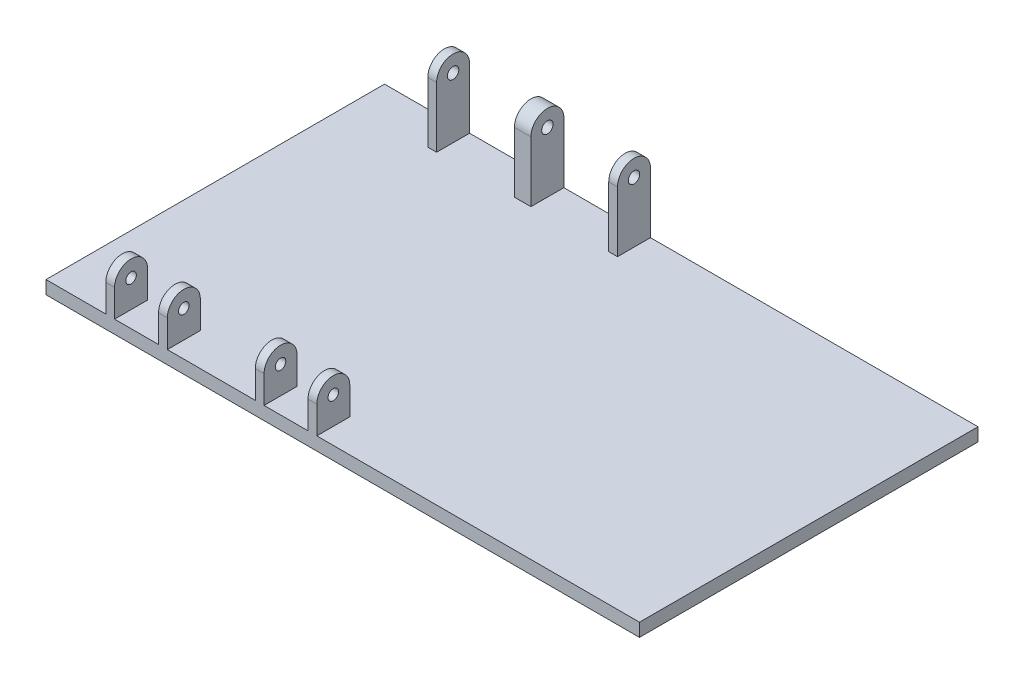
SolidWorks part; units mm, degrees
ref_plane "Front Plane" through (0, 0, 0) normal (0, 0, 1) x (1, 0, 0)
ref_plane "Top Plane" through (0, 0, 0) normal (0, 1, 0) x (1, 0, 0)
ref_plane "Right Plane" through (0, 0, 0) normal (1, 0, 0) x (0, 0, -1)
sketch "Sketch1" plane through (0, 0, 0) normal (0, 1, 0) x (1, 0, 0)
  line L1 (0, 0) -> (342.9, 0)
  line L2 (0, 0) -> (0, 195.58)
  line L3 (0, 195.58) -> (342.9, 195.58)
  line L4 (342.9, 0) -> (342.9, 195.58)
  dimension "D1" = 195.58
  dimension "D2" = 342.9
extrude "Boss-Extrude1" add sketch "Sketch1" along normal blind 7.62 contours L4 L3 L2 L1
sketch "Sketch2" plane through (0, 7.62, 0) normal (0, 1, 0) x (1, 0, 0)
  line L0 (0, 0) -> (342.9, 0) construction
  line L1 (34.5463, 0) -> (39.6263, 0)
  line L2 (34.5463, 0) -> (34.5463, 19.05)
  line L3 (34.5463, 19.05) -> (39.6263, 19.05)
  line L4 (39.6263, 0) -> (39.6263, 19.05)
  line L6 (65.0263, 0) -> (70.1063, 0)
  line L7 (65.0263, 0) -> (65.0263, 19.05)
  line L8 (65.0263, 19.05) -> (70.1063, 19.05)
  line L9 (70.1063, 0) -> (70.1063, 19.05)
  line L10 (120.9063, 0) -> (125.9863, 0)
  line L11 (120.9063, 0) -> (120.9063, 19.05)
  line L12 (120.9063, 19.05) -> (125.9863, 19.05)
  line L13 (125.9863, 0) -> (125.9863, 19.05)
  line L14 (151.3863, 0) -> (156.4663, 0)
  line L15 (151.3863, 0) -> (151.3863, 19.05)
  line L16 (151.3863, 19.05) -> (156.4663, 19.05)
  line L17 (156.4663, 0) -> (156.4663, 19.05)
  line L19 (0, 195.58) -> (342.9, 195.58) construction
  line L21 (49.1513, 195.58) -> (44.0713, 195.58)
  line L22 (49.1513, 195.58) -> (49.1513, 176.53)
  line L23 (49.1513, 176.53) -> (44.0713, 176.53)
  line L24 (44.0713, 195.58) -> (44.0713, 176.53)
  line L25 (94.1093, 195.58) -> (103.6343, 195.58)
  line L26 (94.1093, 195.58) -> (94.1093, 176.53)
  line L27 (94.1093, 176.53) -> (103.6343, 176.53)
  line L28 (103.6343, 195.58) -> (103.6343, 176.53)
  line L33 (148.5923, 195.58) -> (153.6723, 195.58)
  line L34 (148.5923, 195.58) -> (148.5923, 176.53)
  line L35 (148.5923, 176.53) -> (153.6723, 176.53)
  line L36 (153.6723, 195.58) -> (153.6723, 176.53)
  line M12 (0, 0) -> (342.9, 0)
  line M14 (342.9, 195.58) -> (0, 195.58)
  dimension "D1" = 19.05
  dimension "D2" = 5.08
  dimension "D3" = 25.4
  dimension "D4" = 5.08
  dimension "D5" = 19.05
  dimension "D6" = 50.8
  dimension "D7" = 5.08
  dimension "D8" = 19.05
  dimension "D9" = 25.4
  dimension "D10" = 5.08
  dimension "D11" = 19.05
  dimension "D12" = 44.958
  dimension "D13" = 5.08
  dimension "D14" = 5.08
  dimension "D15" = 9.525
  dimension "D16" = 19.05
  dimension "D17" = 19.05
  dimension "D18" = 44.958
extrude "Boss-Extrude2" add sketch "Sketch2" along normal blind 25.4 contours L4 L3 L2 M12 | L9 L8 L7 M12 | L17 L16 L15 M12 | L13 L12 L11 M12 region at (37.0863, 7.62, -9.525) region at (153.9263, 7.62, -9.525) region at (123.4463, 7.62, -9.525) region at (67.5663, 7.62, -9.525)
sketch "Sketch3" plane through (34.5463, 0, 0) normal (-1, 0, 0) x (0, 0, 1)
  line L0 (-19.05, 23.495) -> (-20.422, 33.02)
  line L1 (0, 33.02) -> (0, 7.62) construction
  line L2 (-20.422, 33.02) -> (2.9691, 35.8805)
  line L3 (-19.05, 33.02) -> (-19.05, 7.62) construction
  line L4 (2.9691, 35.8805) -> (0, 23.495)
  arc A0 (-19.05, 23.495) -> (0, 23.495) centre (-9.525, 23.495) cw
  circle A1 centre (-9.525, 23.495) radius 3.048
  dimension "D1" = 6.096
extrude "Cut-Extrude1" cut sketch "Sketch3" against normal through all
extrude "Boss-Extrude3" add sketch "Sketch2<4>" along normal blind 44.45 contours L24 L23 L22 M14 | L28 L26 L27 M14 | L36 L34 L35 M14 region at (46.6113, 7.62, -186.055) region at (151.1323, 7.62, -186.055) region at (98.8718, 7.62, -186.055)
sketch "Sketch2<4>" plane through (0, 7.62, 0) normal (0, 1, 0) x (1, 0, 0) same geometry as "Sketch2"
sketch "Sketch4" plane through (44.0713, 0, 0) normal (-1, 0, 0) x (0, 0, 1)
  line L0 (-195.58, 42.545) -> (-197.5943, 55.0741)
  line L1 (-176.53, 52.07) -> (-176.53, 7.62) construction
  line L2 (-197.5943, 55.0741) -> (-172.1166, 54.4515)
  line L3 (-195.58, 52.07) -> (-195.58, 7.62) construction
  line L4 (-172.1166, 54.4515) -> (-176.53, 42.545)
  circle A0 centre (-186.055, 42.545) radius 3.302
  arc A1 (-195.58, 42.545) -> (-176.53, 42.545) centre (-186.055, 42.545) cw
  dimension "D1" = 6.604
extrude "Cut-Extrude2" cut sketch "Sketch4" along normal through all and the other way blind 492.252
